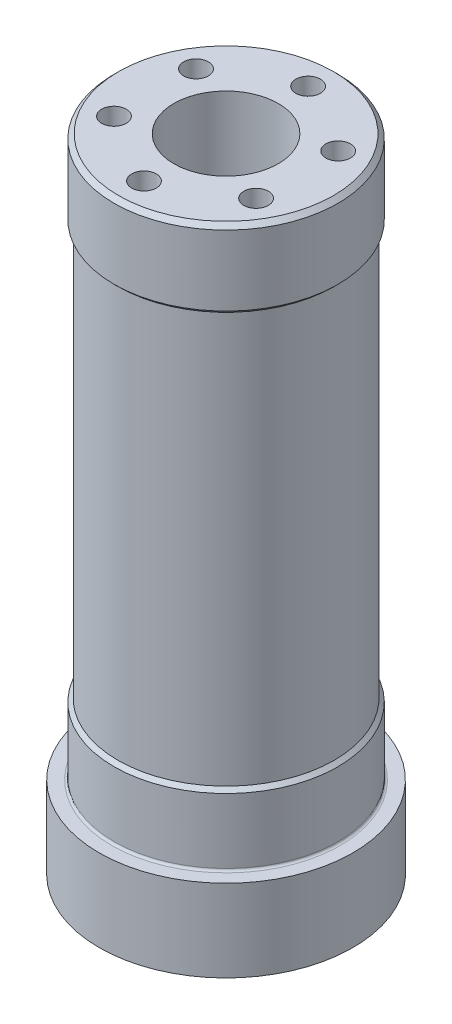
SolidWorks part; units mm, degrees
material "1.4305 (X8CrNiS18-9)"
ref_plane "Front Plane" through (0, 0, 0) normal (0, 0, 1) x (1, 0, 0)
ref_plane "Top Plane" through (0, 0, 0) normal (0, 1, 0) x (1, 0, 0)
ref_plane "Right Plane" through (0, 0, 0) normal (1, 0, 0) x (0, 0, -1)
ref_axis "Elbow" through (0, 110.9595, -40) along (0, -1, 0)
sketch "Sketch1" plane through (0, 0, 0) normal (1, 0, 0) x (0, 0, -1)
  line L0 (55, 27.5) -> (25, 27.5) construction
  line L1 (25, 101.5) -> (55, 101.5) construction
  line L2 (55, 27.5) -> (25, 27.5) construction
  line L3 (25, 101.5) -> (55, 101.5) construction
  line L4 (55, 102.5) -> (55, 92.5)
  line L8 (55, 102.5) -> (47, 102.5)
  line L9 (57, 27.5) -> (57, 20.5)
  line L11 (47, 102.5) -> (47, 14.5)
  line L12 (40, 110.9595) -> (40, -48.0174) construction
  line L13 (55, 27.5) -> (57, 27.5)
  line L17 (57, 16.5) -> (48.5, 16.5)
  line L18 (25, 92.5) -> (55, 92.5) construction
  line L19 (48.5, 16.5) -> (48.5, 14.5)
  line L20 (47, 14.5) -> (48.5, 14.5)
  line L21 (55, 36.5) -> (25, 36.5) construction
  line L22 (25, 92.5) -> (55, 92.5) construction
  line L23 (55, 36.5) -> (25, 36.5) construction
  line L24 (55, 36.5) -> (55, 27.5)
  line L25 (55, 92.5) -> (54.5, 92.5)
  line L26 (54.5, 92.5) -> (54.5, 36.5)
  line L27 (54.5, 36.5) -> (55, 36.5)
  line L28 (57, 20.5) -> (57, 16.5)
  dimension "D1" = 2
  dimension "D2" = 1
  dimension "D3" = 2
  dimension "D4" = 7
  dimension "D5" = 4
  dimension "D6" = 7
  dimension "D8" = 1.5
  dimension "D9" = 0.5
  dimension "D10" = 0
revolve "Revolve1" add sketch "Sketch1" angle 360 about axis through (0, 110.9595, -40) along (0, -1, 0)
sketch "Sketch2" plane through (0, 0, 0) normal (1, 0, 0) x (0, 0, -1)
  line L0 (25, 101.5) -> (55, 101.5) construction
  line L1 (55, 101.5) -> (25, 101.5) construction
  line L4 (47, 106) -> (57, 106)
  line L5 (57, 106) -> (57, 101.5)
  line L6 (57, 101.5) -> (55, 101.5)
  line L7 (55, 101.5) -> (55, 103)
  line L8 (55, 103) -> (47, 103)
  line L9 (47, 106) -> (47, 103)
  line L10 (55, 92.5) -> (55, 102.5) construction
  line L11 (55, 102.5) -> (25, 102.5) construction
  dimension "D1" = 8
  dimension "D2" = 3
  dimension "D3" = 2
  dimension "D4" = 0
  dimension "D5" = 0.5
revolve "Revolve2" add sketch "Sketch2" angle 360 about axis through (0, 110.9595, -40) along (0, -1, 0)
sketch "Sketch8" plane through (0, 106, 0) normal (0, 1, 0) x (1, 0, 0)
  line L0 (0, 55) -> (0, 47) construction
  line L1 (0, 40) -> (0, 51) construction
  circle A0 centre (0, 40) radius 15 construction
  circle A1 centre (0, 40) radius 7 construction
  circle A2 centre (0, 40) radius 15 construction
  circle A3 centre (0, 40) radius 7 construction
  point P17 (0, 51)
  point P24 (9.5263, 45.5)
  point P25 (9.5263, 34.5)
  point P26 (0, 29)
  point P27 (-9.5263, 34.5)
  point P28 (-9.5263, 45.5)
  dimension "D1" = 6
hole_wizard "M4 Clearance Hole2" positions "Sketch8" profile "Sketch6" hole size "M4" standard "DIN" end condition up to next
sketch "Sketch6" plane through (-9.5263, 106, -45.5) normal (1, 0, 0) x (0, 0, 1)
  line L0 (0, 0) -> (0, 89.5)
  line L1 (0, 89.5) -> (2.15, 89.5)
  line L2 (2.15, 89.5) -> (2.15, 0)
  line L5 (2.15, 0) -> (0, 0)
  line L11 (0, -6.35) -> (0, 107.95) construction
  dimension "Thru Hole Dia." = 4.3
  dimension "Thru Hole Depth" = 89.5
sketch "Sketch13" plane through (0, 102.5, 0) normal (0, 1, 0) x (1, 0, 0)
  point P0 (0, 51)
  point P3 (9.5263, 45.5)
  point P6 (9.5263, 34.5)
  point P9 (-9.5263, 45.5)
  point P12 (-9.5263, 34.5)
  point P15 (0, 29)
hole_wizard "M4 Tapped Hole1" positions "Sketch13" profile "Sketch12" tap size "M4" standard "DIN"
sketch "Sketch12" plane through (0, 102.5, -51) normal (1, 0, 0) x (0, 0, 1)
  line L0 (0, 0) -> (0, 12.4914)
  line L1 (0, 12.4914) -> (1.65, 11.5)
  line L2 (1.65, 11.5) -> (1.65, 0)
  line L5 (1.65, 0) -> (0, 0)
  line L10 (0, 12.4914) -> (-1.65, 11.5) construction
  line L11 (0, -6.35) -> (0, 107.95) construction
  dimension "Tap Drill Dia." = 3.3
  dimension "Tap Drill Depth" = 11.5
  dimension "Drill Angle" = 118
cosmetic thread "Hole Thread1" parameters "D1"=8, "D2"=4
cosmetic thread "Hole Thread2" parameters "D1"=8, "D2"=4
cosmetic thread "Hole Thread3" parameters "D1"=8, "D2"=4
cosmetic thread "Hole Thread4" parameters "D1"=8, "D2"=4
cosmetic thread "Hole Thread5" parameters "D1"=8, "D2"=4
cosmetic thread "Hole Thread6" parameters "D1"=8, "D2"=4
sketch "Sketch16" plane through (0, 16.5, 0) normal (0, -1, 0) x (-1, 0, 0)
  point P14 (-9.0156, 49.0156)
  point P17 (9.0156, 49.0156)
  point P20 (-7.2327, 29.5)
  point P23 (7.2327, 29.5)
hole_wizard "M5 Tapped Hole1" positions "Sketch16" profile "Sketch15" tap size "M5" standard "DIN"
sketch "Sketch15" plane through (9.0156, 16.5, -49.0156) normal (1, 0, 0) x (0, 0, -1)
  line L0 (0, 0) -> (0, 11.2618)
  line L1 (0, 11.2618) -> (2.1, 10)
  line L2 (2.1, 10) -> (2.1, 0)
  line L5 (2.1, 0) -> (0, 0)
  line L10 (0, 11.2618) -> (-2.1, 10) construction
  line L11 (0, -6.35) -> (0, 107.95) construction
  dimension "Tap Drill Dia." = 4.2
  dimension "Tap Drill Depth" = 10
  dimension "Drill Angle" = 118
cosmetic thread "Hole Thread7" parameters "D1"=6, "D2"=5
cosmetic thread "Hole Thread8" parameters "D1"=6, "D2"=5
cosmetic thread "Hole Thread9" parameters "D1"=6, "D2"=5
cosmetic thread "Hole Thread10" parameters "D1"=6, "D2"=5
chamfer "Chamfer1" distance 0.6 angle 45 1 edges at (0, 102.5, -25)
fillet "Fillet1" radius 0.3 1 edges at (0, 27.5, -25)
chamfer "Chamfer2" distance 0.5 angle 45 2 edges at (0, 36.5, -25.5) (0, 92.5, -25.5)
fillet "Fillet2" radius 0.4 1 edges at (0, 16.5, -31.5)
fillet "Fillet3" radius 0.4 1 edges at (0, 103, -25)
delete or keep bodies "Body-Delete/Keep 1" type delete bodies bodies 103
delete or keep bodies "Body-Delete/Keep 2" [suppressed] type delete bodies bodies 106
